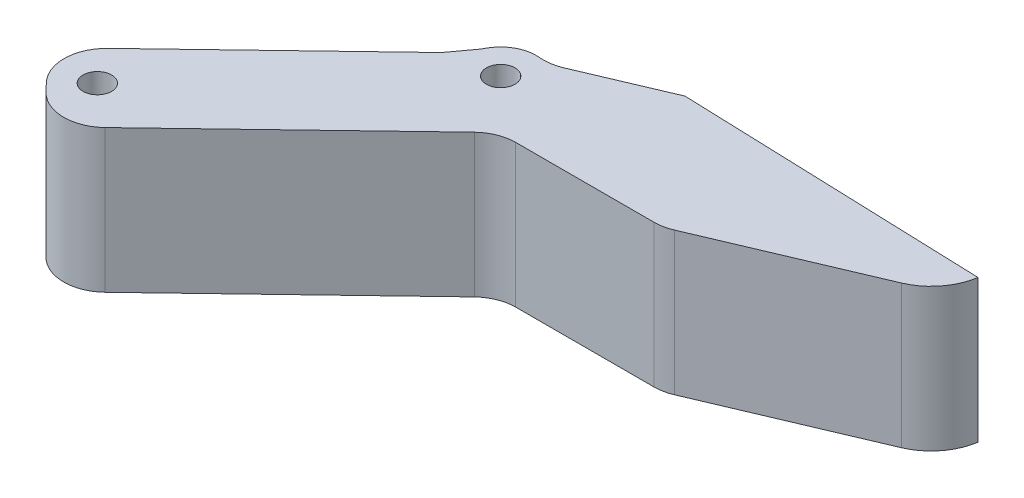
SolidWorks part; units mm, degrees
material "ABS"
ref_plane "Front Plane" through (0, 0, 0) normal (0, 0, 1) x (1, 0, 0)
ref_plane "Top Plane" through (0, 0, 0) normal (0, 1, 0) x (1, 0, 0)
ref_plane "Right Plane" through (0, 0, 0) normal (1, 0, 0) x (0, 0, -1)
sketch "Sketch1" plane through (0, 0, 0) normal (0, 1, 0) x (1, 0, 0)
  line L1 (-8.89, 16.51) -> (73.66, 16.51)
  line L2 (-8.89, 16.51) -> (-8.89, -8.89)
  line L3 (-8.89, -8.89) -> (73.66, -8.89)
  line L4 (73.66, 16.51) -> (73.66, -8.89)
  circle A0 centre (0, 0) radius 2.54
  dimension "D1" = 5.08
  dimension "D2" = 25.4
  dimension "D3" = 8.89
  dimension "D4" = 8.89
  dimension "D5" = 82.55
extrude "Boss-Extrude1" add sketch "Sketch1" along normal blind 25.4
chamfer "Chamfer1" distance 15.24 angle 67 2 edges at (73.66, 12.7, 8.89) (-8.89, 12.7, -16.51) first distance on face at (73.66, 12.7, -3.81) first distance on face at (-8.89, 12.7, -3.81)
fillet "Fillet1" radius 10 1 edges at (73.66, 12.7, -6.35)
chamfer "Chamfer2" distance 5.08 angle 88 1 edges at (73.66, 12.7, -16.51) first distance on face at (73.66, 12.7, -14.7394)
fillet "Fillet2" [suppressed] radius 4.92
sketch "Sketch2" plane through (0, 25.4, 0) normal (0, 1, 0) x (1, 0, 0)
  line L0 (-3.4333, 3.5862) -> (-44.7149, -35.9353)
  line L1 (-3.4333, 3.5862) -> (8.511, -8.89)
  line L2 (-44.7149, -35.9353) -> (-32.7707, -48.4115)
  line L3 (8.511, -8.89) -> (-32.7707, -48.4115)
  line L4 (19.501, 13.3213) -> (-8.89, 1.27) construction
  line L5 (-8.89, -8.89) -> (37.7568, -8.89) construction
  point P0 (10.7825, -8.89)
  dimension "D1" = 57.15
  dimension "D2" = 17.272
extrude "Boss-Extrude2" add sketch "Sketch2" against normal blind 25.4
sketch "Sketch3" plane through (0, 25.4, 0) normal (0, 1, 0) x (1, 0, 0)
  line L0 (1.7565, -1.8347) -> (-1.7565, 1.8347) construction
  circle A0 centre (0, 0) radius 2.54
extrude "Cut-Extrude1" cut sketch "Sketch3" against normal through all
sketch "Sketch4" plane through (0, 25.4, 0) normal (0, 1, 0) x (1, 0, 0)
  line L0 (-8.89, -1.6378) -> (-44.7149, -35.9353) construction
  circle A0 centre (-34.8084, -37.0002) radius 2.54
  circle A1 centre (0, 0) radius 2.54 construction
  dimension "D1" = 5.08
  dimension "D2" = 50.8
  dimension "D3" = 7.62
extrude "Cut-Extrude2" cut sketch "Sketch4" against normal through all
fillet "Fillet3" radius 7.62 2 edges at (-32.7707, 12.7, 48.4115) (-44.7149, 12.7, 35.9353)
fillet "Fillet4" radius 7.62 2 edges at (8.511, 12.7, 8.89) (37.7568, 12.7, 8.89)
sketch "Sketch5" plane through (0, 25.4, 0) normal (0, 1, 0) x (1, 0, 0)
  circle A0 centre (0, 0) radius 6.35
  circle A1 centre (0, 0) radius 2.54
  dimension "D1" = 12.7
extrude "Boss-Extrude3" add sketch "Sketch5" against normal blind 25.4
fillet "Fillet5" radius 7.62 1 edges at (2.1738, 12.7, -5.9663)
sketch "Sketch6" plane through (0, 25.4, 0) normal (0, 1, 0) x (1, 0, 0)
  line L0 (-5.8019, 2.5808) -> (-8.89, -1.6378)
  line L1 (-8.89, -1.6378) -> (-8.89, 1.27)
  line L2 (-8.89, 1.27) -> (-5.8019, 2.5808)
extrude "Cut-Extrude3" cut sketch "Sketch6" against normal through all
fillet "Fillet6" radius 7.62 2 edges at (-8.89, 12.7, 1.6378) (-5.8019, 12.7, -2.5808)
